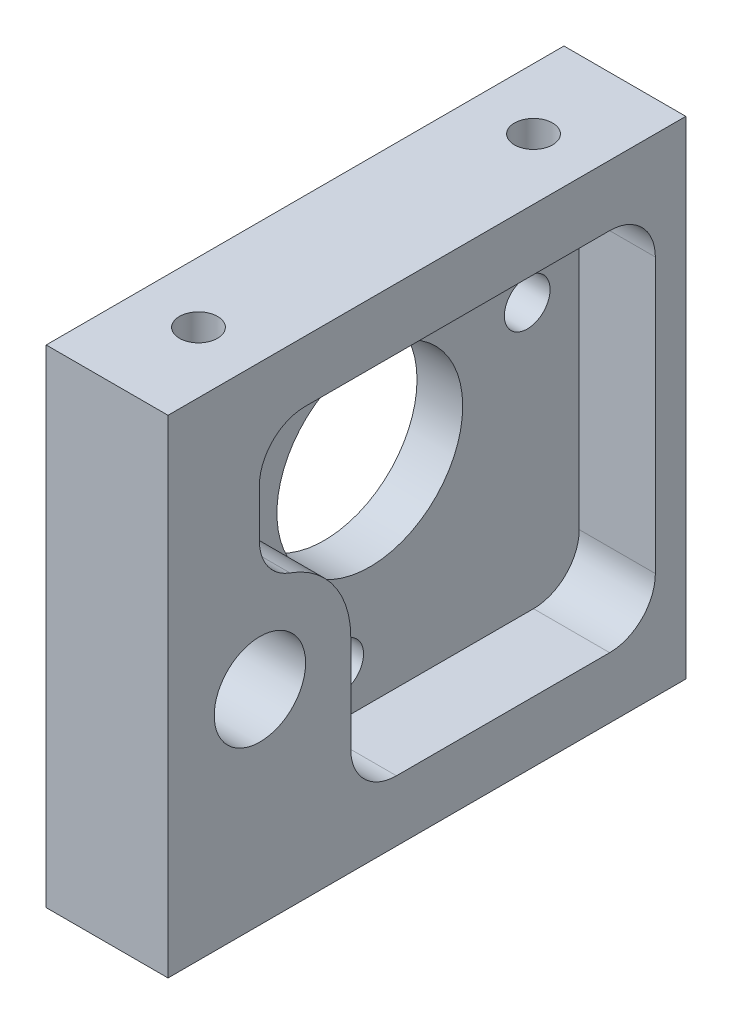
SolidWorks part; units mm, degrees
ref_plane "Front Plane" through (0, 0, 0) normal (0, 0, 1) x (1, 0, 0)
ref_plane "Top Plane" through (0, 0, 0) normal (0, 1, 0) x (1, 0, 0)
ref_plane "Right Plane" through (0, 0, 0) normal (1, 0, 0) x (0, 0, -1)
sketch "Sketch1" plane through (0, 0, 0) normal (1, 0, 0) x (0, 0, -1)
  line L1 (0, 0) -> (34, 0)
  line L2 (0, 0) -> (0, 32)
  line L3 (0, 32) -> (34, 32)
  line L4 (34, 0) -> (34, 32)
  dimension "D1" = 32
  dimension "D2" = 34
extrude "Boss-Extrude1" add sketch "Sketch1" along normal blind 8
sketch "Sketch2" plane through (8, 0, 0) normal (1, 0, 0) x (0, 0, -1)
  line L0 (28.5866, 21.6122) -> (6.034, 13.4037) construction
  line L1 (0, 0) -> (34, 0) construction
  line L2 (0, 32) -> (0, 0) construction
  circle A0 centre (18.25, 17.85) radius 6.1
  circle A1 centre (6.034, 13.4037) radius 3
  circle A2 centre (28.5866, 21.6122) radius 1.5
  dimension "D2" = 12.2
  dimension "D3" = 3
  dimension "D6" = 6
  dimension "D1" = 13
  dimension "D4" = 20
  dimension "D5" = 11
  dimension "D7" = 17.85
  dimension "D8" = 18.25
extrude "Cut-Extrude1" cut sketch "Sketch2" against normal up to next
pattern_circular "CirPattern1" count 3 over 360 about axis through (8, 17.85, -18.25) along (1, 0, 0) of face at (0, 21.6122, -27.0866)
sketch "Sketch3" plane through (8, 0, 0) normal (1, 0, 0) x (0, 0, -1)
  line L0 (32, 25) -> (32, 7)
  line L1 (29, 4) -> (15, 4)
  line L2 (12, 7) -> (12, 13.4037)
  line L3 (6, 21.8649) -> (6, 25)
  line L4 (9, 28) -> (29, 28)
  line L5 (34, 0) -> (34, 32) construction
  line L6 (0, 0) -> (34, 0) construction
  line L7 (34, 32) -> (0, 32) construction
  line L8 (0, 32) -> (0, 0) construction
  arc A0 (12, 13.4037) -> (8.0076, 19.0338) centre (6.034, 13.4037) ccw
  arc A1 (8.0076, 19.0338) -> (6, 21.8649) centre (9, 21.8649) cw
  arc A2 (15, 4) -> (12, 7) centre (15, 7) cw
  arc A3 (32, 7) -> (29, 4) centre (29, 7) cw
  arc A4 (32, 25) -> (29, 28) centre (29, 25) ccw
  arc A5 (6, 25) -> (9, 28) centre (9, 25) cw
  dimension "D4" = 3
  dimension "D5" = 3
  dimension "D1" = 2
  dimension "D2" = 4
  dimension "D3" = 4
  dimension "D6" = 6
  dimension "D7" = 12
extrude "Cut-Extrude2" cut sketch "Sketch3" against normal blind 5
hole_wizard "Tap Drill for M3x0.5 Tap1" positions "Sketch5" profile "Sketch4" hole size "M3x0.5" standard "ANSI Metric"
sketch "Sketch5" plane through (0, 32, 0) normal (0, 1, 0) x (-1, 0, 0)
  line L0 (0, -34) -> (0, 0) construction
  line L1 (-8, 0) -> (0, 0) construction
  line L2 (-8, -34) -> (0, -34) construction
  point P0 (-4, -6)
  point P2 (-4, -28)
  dimension "D1" = 4
  dimension "D2" = 6
  dimension "D3" = 6
sketch "Sketch4" plane through (4, 32, -6) normal (1, 0, 0) x (0, 0, 1)
  line L0 (0, 0) -> (0, 3.7511)
  line L1 (0, 3.7511) -> (1.25, 3)
  line L2 (1.25, 3) -> (1.25, 0)
  line L5 (1.25, 0) -> (0, 0)
  line L10 (0, 3.7511) -> (-1.25, 3) construction
  line L11 (0, -6.35) -> (0, 107.95) construction
  dimension "Hole Dia." = 2.5
  dimension "Hole Depth" = 3
  dimension "Drill Angle" = 118
hole_wizard "Tap Drill for M3x0.5 Tap2" positions "Sketch7" profile "Sketch6" hole size "M3x0.5" standard "ANSI Metric"
sketch "Sketch7" plane through (0, 0, 0) normal (0, -1, 0) x (1, 0, 0)
  line L0 (8, 0) -> (0, 0) construction
  line L1 (8, -34) -> (0, -34) construction
  line L2 (8, 0) -> (8, -34) construction
  point P0 (4, -6)
  point P2 (4, -28)
  dimension "D1" = 6
  dimension "D2" = 6
  dimension "D3" = 4
sketch "Sketch6" plane through (4, 0, -6) normal (1, 0, 0) x (0, 0, -1)
  line L0 (0, 0) -> (0, 3.7511)
  line L1 (0, 3.7511) -> (1.25, 3)
  line L2 (1.25, 3) -> (1.25, 0)
  line L5 (1.25, 0) -> (0, 0)
  line L10 (0, 3.7511) -> (-1.25, 3) construction
  line L11 (0, -6.35) -> (0, 107.95) construction
  dimension "Hole Dia." = 2.5
  dimension "Hole Depth" = 3
  dimension "Drill Angle" = 118
